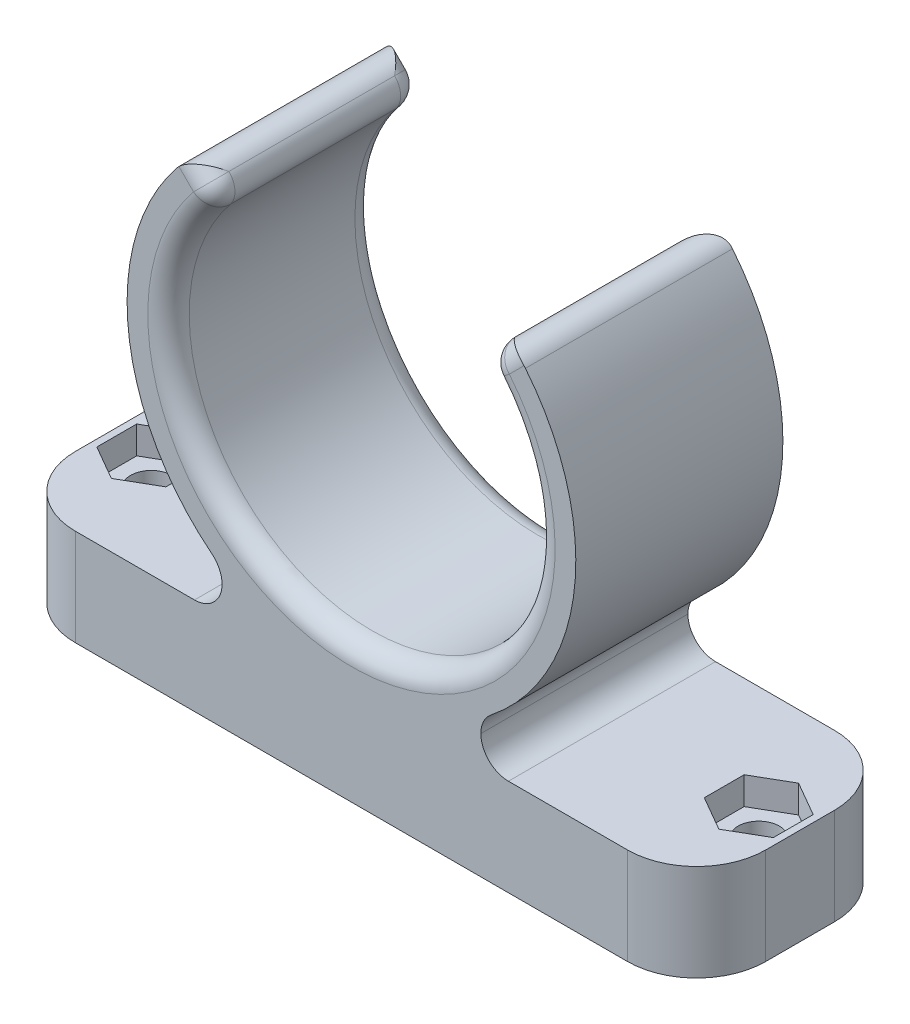
SolidWorks part; units mm, degrees
ref_plane "Plano frontal" through (0, 0, 0) normal (0, 0, 1) x (1, 0, 0)
ref_plane "Plano superior" through (0, 0, 0) normal (0, 1, 0) x (1, 0, 0)
ref_plane "Plano direito" through (0, 0, 0) normal (1, 0, 0) x (0, 0, -1)
sketch "Esboço2" plane through (0, 0, 0) normal (0, 0, 1) x (1, 0, 0)
  line L0 (0, 0) -> (0, -10) construction
  line L1 (-25, -10) -> (25, -10)
  line L2 (25, -10) -> (25, -3)
  line L3 (-25, -3) -> (-9.3692, -3)
  line L4 (9.3692, 22.6192) -> (25, 38.25)
  line L5 (0, 0) -> (0, 13.25) construction
  line L6 (25, 38.25) -> (25, -3) construction
  line L7 (-9.3692, 22.6192) -> (-11.4905, 24.7405)
  line L8 (-25, -10) -> (-25, -3)
  line L9 (25, -3) -> (9.3692, -3)
  line L10 (-9.3692, -0.0271) -> (-9.3692, -3)
  line L11 (9.3692, -0.0271) -> (9.3692, -3)
  line L12 (25, -3) -> (9.3692, -3)
  arc A0 (-9.3692, 22.6192) -> (9.3692, 22.6192) centre (0, 13.25) ccw
  arc A1 (-11.4905, 24.7405) -> (-9.3692, -0.0271) centre (0, 13.25) ccw
  arc A2 (9.3692, -0.0271) -> (11.4905, 24.7405) centre (0, 13.25) ccw
  arc A3 (9.3692, -0.0271) -> (-9.3692, -0.0271) centre (0, 13.25) ccw
  point P19 (9.6933, 0.2077)
  dimension "D4" = 13.25
  dimension "D5" = 3
  dimension "D1" = 10
  dimension "D2" = 45
  dimension "D3" = 50
extrude "Ressalto-extrusão1" add sketch "Esboço2" along normal blind 15 contours A2 L4 A0 L7 A1 L8 L1 L2 region at (0, -0.8262, 0)
sketch "Esboço3" plane through (0, -3, 0) normal (0, 1, 0) x (1, 0, 0)
  line L0 (0, 0) -> (0, -15) construction
  line L1 (-25, 0) -> (25, 0) construction
  line L2 (-25, -15) -> (25, -15) construction
  line L3 (22, -15) -> (22, 0) construction
  line L5 (25, -15) -> (25, 0) construction
  circle A0 centre (22, -7.5) radius 1.5
  circle A1 centre (-22, -7.5) radius 1.5
  point P10 (21.8323, 0)
  point P12 (19.218, 0)
  point P13 (19.218, -7.5)
  dimension "D1" = 3
extrude "Corte-extrusão1" cut sketch "Esboço3" against normal up to surface (7 mm away) up to face at (0, -10, 7.5)
sketch "Esboço5" plane through (0, -3, 0) normal (0, 1, 0) x (1, 0, 0)
  line L1 (22, -4.6132) -> (19.5, -6.0566)
  line L2 (19.5, -6.0566) -> (19.5, -8.9434)
  line L3 (19.5, -8.9434) -> (22, -10.3868)
  line L4 (22, -10.3868) -> (24.5, -8.9434)
  line L5 (24.5, -8.9434) -> (24.5, -6.0566)
  line L6 (24.5, -6.0566) -> (22, -4.6132)
  line L7 (0, 0) -> (0, -14.5158)
  line L8 (-24.5, -6.0566) -> (-22, -4.6132)
  line L9 (-24.5, -8.9434) -> (-24.5, -6.0566)
  line L10 (-22, -10.3868) -> (-24.5, -8.9434)
  line L11 (-19.5, -8.9434) -> (-22, -10.3868)
  line L12 (-19.5, -6.0566) -> (-19.5, -8.9434)
  line L13 (-22, -4.6132) -> (-19.5, -6.0566)
  circle A1 centre (22, -7.5) radius 1.5
  circle A2 centre (22, -7.5) radius 2.5 construction
  circle A3 centre (-22, -7.5) radius 2.5 construction
  circle A4 centre (-22, -7.5) radius 1.5
extrude "Corte-extrusão2" cut sketch "Esboço5" against normal blind 2 contours L5 L6 L1 L2 L3 L4 | L13 L8 L9 L10 L11 L12 A4 region at (23.2118, -3, 5.4011) region at (-23.2118, -3, 5.4011)
fillet "Filete1" radius 1.5 10 edges at (0, 0, 15) (0, 0, 0) (11.4905, 24.7405, 7.5) (10.4298, 23.6798, 15) (9.3692, 22.6192, 7.5) (10.4298, 23.6798, 0) (-9.3692, 22.6192, 7.5) (-10.4298, 23.6798, 15) (-11.4905, 24.7405, 7.5) (-10.4298, 23.6798, 0)
fillet "Filete2" radius 2 4 edges at (9.3692, -0.0271, 7.5) (9.3692, -3, 7.5) (-9.3692, -0.0271, 7.5) (-9.3692, -3, 7.5)
fillet "Filete3" radius 5 4 edges at (25, -6.5, 0) (25, -6.5, 15) (-25, -6.5, 0) (-25, -6.5, 15)
